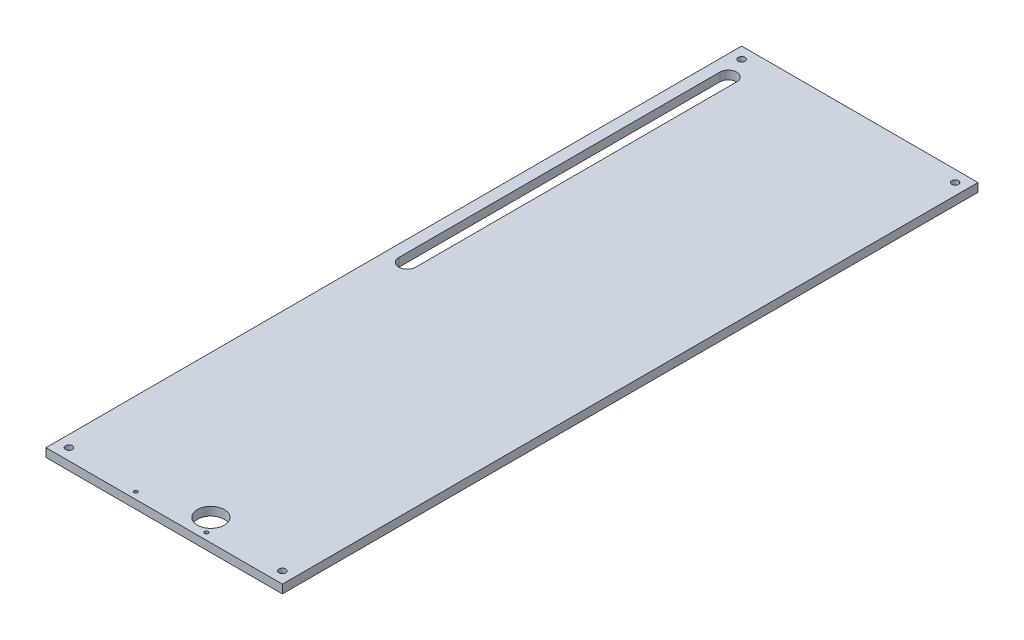
SolidWorks part; units mm, degrees
ref_plane "Front Plane" through (0, 0, 0) normal (0, 0, 1) x (1, 0, 0)
ref_plane "Top Plane" through (0, 0, 0) normal (0, 1, 0) x (1, 0, 0)
ref_plane "Right Plane" through (0, 0, 0) normal (1, 0, 0) x (0, 0, -1)
sketch "Sketch2" plane through (0, 0, 0) normal (0, 0, 1) x (1, 0, 0)
  line L0 (42.8242, -21.393) -> (42.8242, -24.5934)
  line L1 (0, -21.393) -> (0, -24.5934) construction
  line L2 (-46.0758, -24.5934) -> (42.8242, -24.5934)
  line L3 (-46.0758, -21.393) -> (-46.0758, -24.5934)
  line L4 (-46.0758, -21.393) -> (42.8242, -21.393)
  dimension "D1" = 88.9
  dimension "D2" = 3.2004
extrude "Boss-Extrude1" add sketch "Sketch2" along normal blind 261.62 contours L2 L0 L4 L3
sketch "Sketch3" plane through (0, -21.393, 0) normal (0, 1, 0) x (-1, 0, 0)
  line L0 (-42.8242, 259.08) -> (46.0758, 259.08) construction
  line L1 (38.5043, 9.421) -> (38.5043, 0) construction
  line L2 (46.0758, 0) -> (-42.8242, 0) construction
  line L3 (46.0758, 261.62) -> (-42.8242, 261.62) construction
  line L4 (41.7578, 257.302) -> (46.0758, 257.302) construction
  line L5 (46.0758, 72.9493) -> (41.6793, 72.9493) construction
  line L6 (35.3293, 12.596) -> (41.6793, 12.596) construction
  line L7 (35.3293, 12.596) -> (35.3293, 133.3026)
  line L8 (35.3293, 133.3026) -> (41.6793, 133.3026) construction
  line L9 (41.6793, 12.596) -> (41.6793, 133.3026)
  line L10 (46.0758, 261.62) -> (-42.8242, 261.62) construction
  line L11 (-11.6838, 259.08) -> (-11.6838, 261.62) construction
  line L12 (-11.6838, 253.3188) -> (-11.6838, 259.08) construction
  line L13 (-7.6198, 253.3188) -> (-11.6838, 253.3188) construction
  line L14 (-42.8242, 261.62) -> (-42.8242, 0) construction
  line L15 (46.0758, 261.62) -> (46.0758, 0) construction
  line L16 (-38.5062, 257.302) -> (-38.5062, 261.62) construction
  line L17 (-38.5062, 257.302) -> (-42.8242, 257.302) construction
  line L18 (41.7578, 257.302) -> (41.7578, 261.62) construction
  line L19 (-38.5062, 4.318) -> (-42.8242, 4.318) construction
  line L20 (-38.5062, 4.318) -> (-38.5062, 0) construction
  line L21 (46.0758, 0) -> (-42.8242, 0) construction
  line L22 (41.7578, 4.318) -> (41.7578, 0) construction
  line L23 (41.7578, 4.318) -> (46.0758, 4.318) construction
  circle A0 centre (14.8338, 259.08) radius 0.6731
  arc A1 (35.3293, 133.3026) -> (41.6793, 133.3026) centre (38.5043, 133.3026) cw
  arc A2 (41.6793, 12.596) -> (35.3293, 12.596) centre (38.5043, 12.596) cw
  circle A3 centre (-11.6838, 259.08) radius 0.6731
  circle A4 centre (-7.6198, 253.3188) radius 5.08
  circle A5 centre (-38.5062, 257.302) radius 1.27
  circle A6 centre (41.7578, 257.302) radius 1.27
  circle A7 centre (-38.5062, 4.318) radius 1.27
  circle A8 centre (41.7578, 4.318) radius 1.27
  point P12 (1.6258, 259.08)
  dimension "D5" = 1.3462
  dimension "D9" = 10.16
  dimension "D13" = 2.54
  dimension "D2" = 4.3965
  dimension "D3" = 120.7066
  dimension "D4" = 6.35
  dimension "D6" = 2.54
  dimension "D7" = 26.5176
  dimension "D8" = 13.208
  dimension "D10" = 5.7612
  dimension "D11" = 4.064
  dimension "D12" = 9.421
  dimension "D14" = 4.318
extrude "Cut-Extrude1" cut sketch "Sketch3" against normal through all
